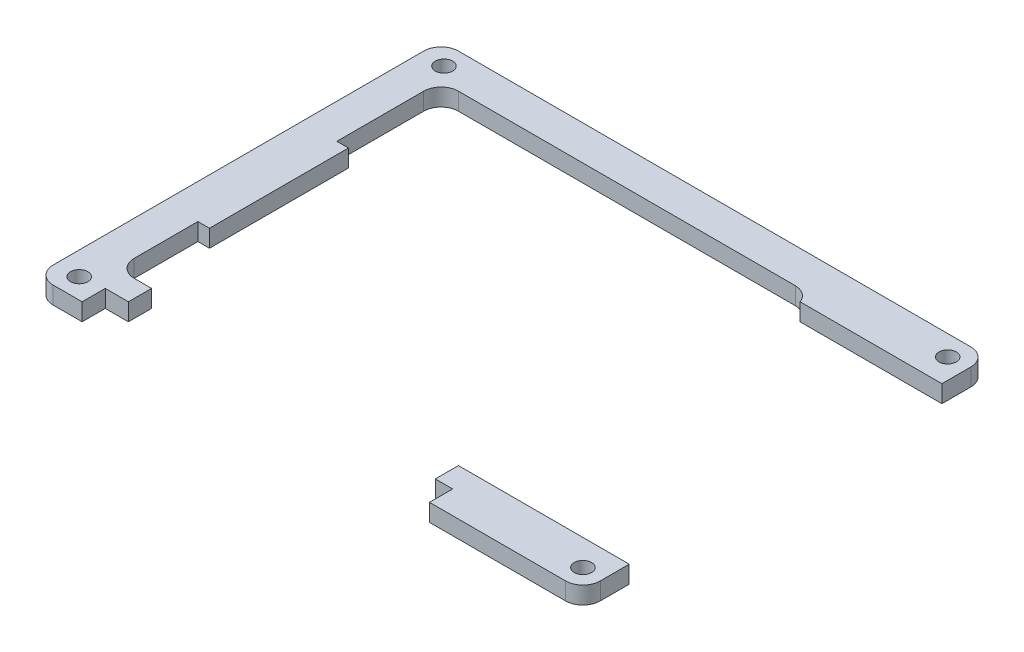
SolidWorks part; units mm, degrees
material "ABS"
ref_plane "Front Plane" through (0, 0, 0) normal (0, 0, 1) x (1, 0, 0)
ref_plane "Top Plane" through (0, 0, 0) normal (0, 1, 0) x (1, 0, 0)
ref_plane "Right Plane" through (0, 0, 0) normal (1, 0, 0) x (0, 0, -1)
sketch "Sketch1" plane through (0, 0, 0) normal (0, 1, 0) x (1, 0, 0)
  line L1 (-47.25, 35) -> (47.25, 35)
  line L2 (-47.25, 35) -> (-47.25, -35)
  line L3 (-47.25, -35) -> (47.25, -35)
  line L4 (47.25, 35) -> (47.25, -35)
  line L5 (-47.25, 35) -> (47.25, -35) construction
  line L6 (-47.25, -35) -> (47.25, 35) construction
  point P0 (0, 0)
  dimension "D1" = 70
  dimension "D2" = 94.5
extrude "Boss-Extrude1" add sketch "Sketch1" along normal blind 3
sketch "Sketch3" plane through (0, 3, 0) normal (0, 1, 0) x (1, 0, 0)
  line L0 (47.25, -35) -> (47.25, 35) construction
  line L2 (47.25, 35) -> (-47.25, 35) construction
  circle A0 centre (43.75, 31.5) radius 1.5
  circle A1 centre (-43.25, 31.5) radius 1.5
  circle A2 centre (-43.25, -31.5) radius 1.5
  circle A3 centre (43.75, -31.5) radius 1.5
  dimension "D1" = 3
  dimension "D2" = 3.5
  dimension "D3" = 3.5
  dimension "D4" = 2
  dimension "D5" = 87
  dimension "D6" = 63
  dimension "D7" = 2
extrude "Cut-Extrude2" cut sketch "Sketch3" against normal through all
fillet "Fillet2" radius 3 4 edges at (-47.25, 1.5, 35) (-47.25, 1.5, -35) (47.25, 1.5, -35) (47.25, 1.5, 35)
sketch "Sketch5" plane through (0, 3, 0) normal (0, 1, 0) x (1, 0, 0)
  line L0 (-41.25, 29) -> (22.75, 29)
  line L1 (22.75, 29) -> (22.75, -27)
  line L2 (22.75, -27) -> (-41.25, -27)
  line L3 (-41.25, -27) -> (-41.25, 29)
  line L4 (47.25, 27) -> (22.75, 27)
  line L5 (47.25, -32) -> (47.25, 32) construction
  line L8 (47.25, -27) -> (47.25, 27)
  line L17 (44.25, 35) -> (-44.25, 35) construction
  line L18 (-47.25, 32) -> (-47.25, -32) construction
  line L19 (-35.25, -27) -> (-35.25, -31)
  line L20 (-35.25, -31) -> (-39.25, -31)
  line L21 (-39.25, -31) -> (-39.25, -35)
  line L22 (-44.25, -35) -> (44.25, -35) construction
  line L23 (-39.25, -35) -> (20.75, -35)
  line L24 (20.75, -35) -> (20.75, -31)
  line L25 (20.75, -31) -> (17.75, -31)
  line L26 (17.75, -31) -> (17.75, -27)
  line L27 (-41.25, 11) -> (-39.25, 11)
  line L28 (-39.25, 11) -> (-39.25, -13)
  line L29 (-39.25, -13) -> (-41.25, -13)
  line L30 (47.25, -27) -> (22.75, -27)
  line M19 (-44.25, -35) -> (44.25, -35)
  line M21 (47.25, -32) -> (47.25, 32)
  dimension "D1" = 6
  dimension "D2" = 6
  dimension "D3" = 64
  dimension "D4" = 56
  dimension "D5" = 24
  dimension "D6" = 24
  dimension "D7" = 8
  dimension "D9" = 8
  dimension "D14" = 60
  dimension "D15" = 8
  dimension "D16" = 53
  dimension "D17" = 4
  dimension "D18" = 12
extrude "Cut-Extrude3" cut sketch "Sketch5" against normal through all contours L28 L29 L3 L2 L1 L0 L27 | L25 L26 L2 L19 L20 L21 L24 M19 | L30 L4 L1 M21 region at (-8.8292, 3, -1.0271) region at (35, 3, 0) region at (-9.0155, 3, 31.1239)
fillet "Fillet3" radius 3 3 edges at (22.75, 1.5, -29) (-41.25, 1.5, 27) (-41.25, 1.5, -29)
